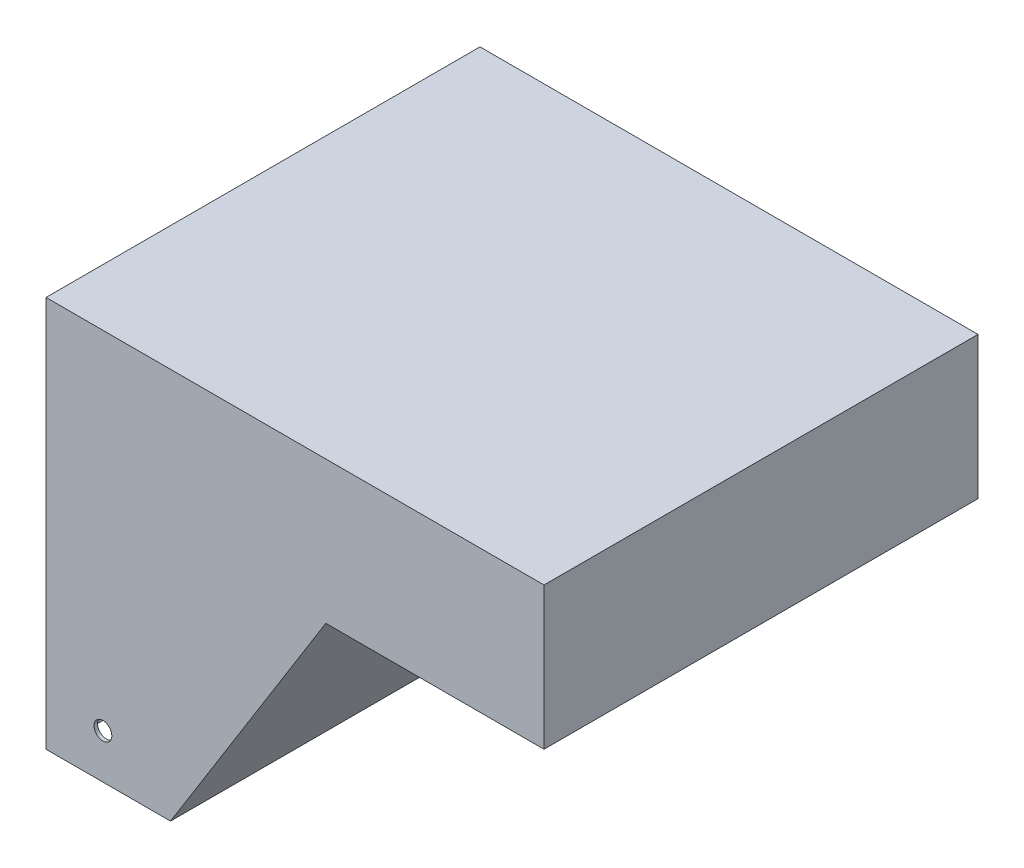
SolidWorks part; units mm, degrees
material "Acrylic (Medium-high impact)"
ref_plane "Front Plane" through (0, 0, 0) normal (0, 0, 1) x (1, 0, 0)
ref_plane "Top Plane" through (0, 0, 0) normal (0, 1, 0) x (1, 0, 0)
ref_plane "Right Plane" through (0, 0, 0) normal (1, 0, 0) x (0, 0, -1)
sketch "Sketch2" plane through (0, 0, 0) normal (0, 0, 1) x (1, 0, 0)
  line L0 (0, 0) -> (355.6, 0)
  line L1 (355.6, 0) -> (355.6, -101.6)
  line L2 (355.6, -101.6) -> (199.8078, -101.6)
  line L3 (199.8078, -101.6) -> (88.9, -279.4)
  line L4 (88.9, -279.4) -> (0, -279.4)
  line L5 (0, -279.4) -> (0, 0)
  circle A0 centre (40.64, -247.65) radius 6.35
  dimension "D6" = 12.7
  dimension "D1" = 355.6
  dimension "D2" = 279.4
  dimension "D3" = 101.6
  dimension "D4" = 88.9
  dimension "D5" = 31.75
  dimension "D7" = 40.64
extrude "Boss-Extrude1" add sketch "Sketch2" along normal blind 2.54
sketch "Sketch3" plane through (0, 0, 2.54) normal (0, 0, 1) x (1, 0, 0)
  line L6 (2.54, -276.86) -> (2.54, -279.4)
  line L7 (0, -279.4) -> (88.9, -279.4) construction
  line L8 (87.4908, -276.86) -> (87.4908, -279.4)
  line L12 (2.54, -2.54) -> (2.54, -276.86)
  line L13 (2.54, -276.86) -> (87.4908, -276.86)
  line L14 (87.4908, -276.86) -> (198.3986, -99.06)
  line L15 (198.3986, -99.06) -> (353.06, -99.06)
  line L16 (353.06, -99.06) -> (353.06, -2.54)
  line L17 (353.06, -2.54) -> (2.54, -2.54)
  line L18 (2.54, -2.54) -> (2.54, -276.86)
  line L20 (87.4908, -276.86) -> (198.3986, -99.06)
  line L21 (198.3986, -99.06) -> (353.06, -99.06)
  line L22 (353.06, -99.06) -> (353.06, -2.54)
  line L23 (353.06, -2.54) -> (2.54, -2.54)
  line M7 (0, 0) -> (0, -279.4)
  line M8 (0, -279.4) -> (88.9, -279.4)
  line M9 (88.9, -279.4) -> (199.8078, -101.6)
  line M10 (199.8078, -101.6) -> (355.6, -101.6)
  line M11 (355.6, -101.6) -> (355.6, 0)
  line M12 (355.6, 0) -> (0, 0)
  dimension "D1" = 2.54
extrude "Boss-Extrude2" add sketch "Sketch3" along normal blind 304.8 contours L23 L22 L21 L20 L18 M12 M7 M8 M9 M10 M11 region at (2.0878, -278.13, 2.54)
ref_plane "Plane1" through (0, 0, 154.94) normal (0, 0, 1) x (1, 0, 0)
mirror "Mirror1" about plane through (0, 0, 154.94) normal (0, 0, 1) of "Boss-Extrude1"
sketch "Sketch4" plane through (0, 0, 0) normal (-1, 0, 0) x (0, 0, 1)
  line L0 (309.88, -279.4) -> (0, -279.4) construction
  line L1 (120.015, -244.851) -> (189.865, -244.851) construction
  circle A0 centre (120.015, -244.851) radius 1.5875
  circle A1 centre (120.015, -270.251) radius 1.5875
  circle A2 centre (189.865, -244.851) radius 1.5875
  circle A3 centre (189.865, -270.251) radius 1.5875
  point P8 (154.94, -279.4)
  point P9 (154.94, -244.851)
  dimension "D1" = 3.175
  dimension "D2" = 69.85
  dimension "D3" = 25.4
extrude "Cut-Extrude1" cut sketch "Sketch4" against normal up to next
